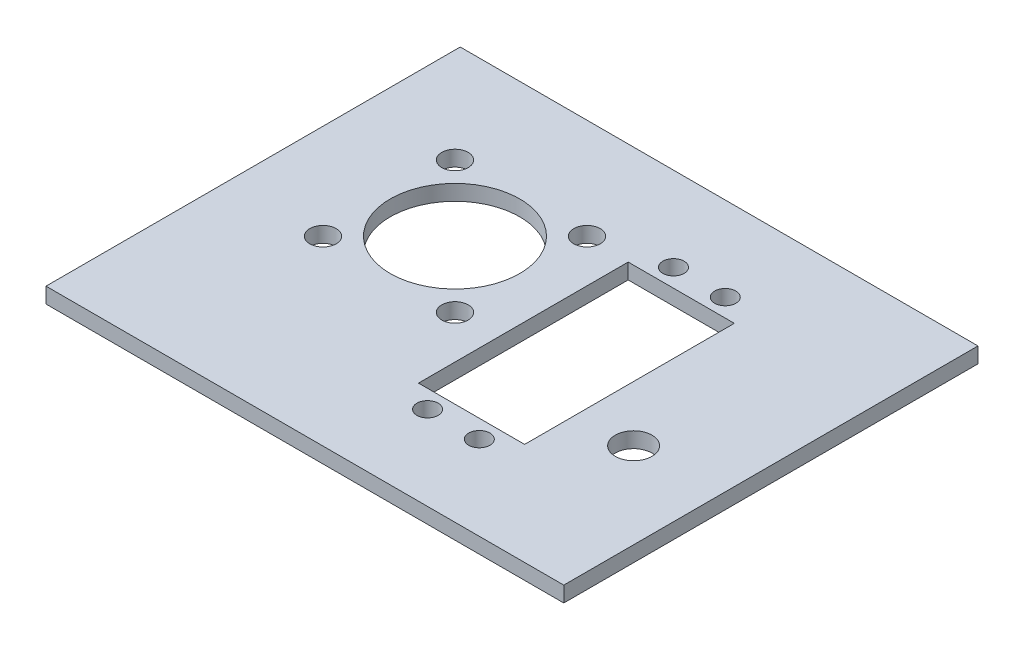
SolidWorks part; units mm, degrees
ref_plane "Płaszczyzna przednia" through (0, 0, 0) normal (0, 0, 1) x (1, 0, 0)
ref_plane "Płaszczyzna górna" through (0, 0, 0) normal (0, 1, 0) x (1, 0, 0)
ref_plane "Płaszczyzna prawa" through (0, 0, 0) normal (1, 0, 0) x (0, 0, -1)
sketch "Szkic1" plane through (0, 0, 0) normal (0, 1, 0) x (1, 0, 0)
  line L6 (-20.2688, 11.7569) -> (5.2312, -13.7431) construction
  line L11 (-38.6633, 31.161) -> (61.3367, 31.161)
  line L12 (-38.6633, 31.161) -> (-38.6633, -48.839)
  line L13 (-38.6633, -48.839) -> (61.3367, -48.839)
  line L14 (61.3367, 31.161) -> (61.3367, -48.839)
  line L15 (-20.2688, -13.7431) -> (5.2312, 11.7569) construction
  line L17 (13.5251, 11.411) -> (34.0251, 11.411)
  line L18 (13.5251, 11.411) -> (13.5251, -29.089)
  line L23 (13.5251, -29.089) -> (34.0251, -29.089)
  line L24 (34.0251, 11.411) -> (34.0251, -29.089)
  circle A0 centre (-7.5188, -0.9931) radius 12.5
  circle A2 centre (-20.2688, 11.7569) radius 2.55
  circle A3 centre (5.2312, 11.7569) radius 2.55
  circle A4 centre (5.2312, -13.7431) radius 2.55
  circle A5 centre (-20.2688, -13.7431) radius 2.55
  circle A6 centre (18.7751, 14.911) radius 2.05
  circle A7 centre (28.7751, 14.911) radius 2.05
  circle A8 centre (18.7751, -32.589) radius 2.05
  circle A9 centre (28.7751, -32.589) radius 2.05
  circle A10 centre (23.7751, -18.789) radius 0.5
  circle A11 centre (-7.5188, -0.9931) radius 0.5
  circle A12 centre (44.7751, -18.789) radius 3.55
  circle A13 centre (44.7751, -18.789) radius 0.5
  point P18 (23.7751, -29.089)
  point P22 (23.7751, 11.411)
  dimension "D3" = 10.3
  dimension "D5" = 3.5
  dimension "D13" = 36
  dimension "D18" = 19.75
  dimension "D20" = 5.1
  dimension "D22" = 25
  dimension "D23" = 7.1
  dimension "D24" = 4.1
  dimension "D25" = 47.5
  dimension "D1" = 100
  dimension "D2" = 80
  dimension "D4" = 10.25
  dimension "D6" = 3.5
  dimension "D7" = 5
  dimension "D8" = 5
  dimension "D9" = 3.5
  dimension "D10" = 3.5
  dimension "D11" = 5
  dimension "D12" = 5
  dimension "D14" = 21
  dimension "D15" = 40.5
  dimension "D16" = 20.5
  dimension "D17" = 10.3
  dimension "D19" = 19.75
  dimension "D21" = 25.5
extrude "Dodanie-wyciągnięcie1" add sketch "Szkic1" along normal blind 3 contours L14 L11 L12 L13 A12 A9 A8 A7 A6 A5 A4 A3 A2 A0 L17 L24 L23 L18 region at (11.1044, 0, 9.469)
